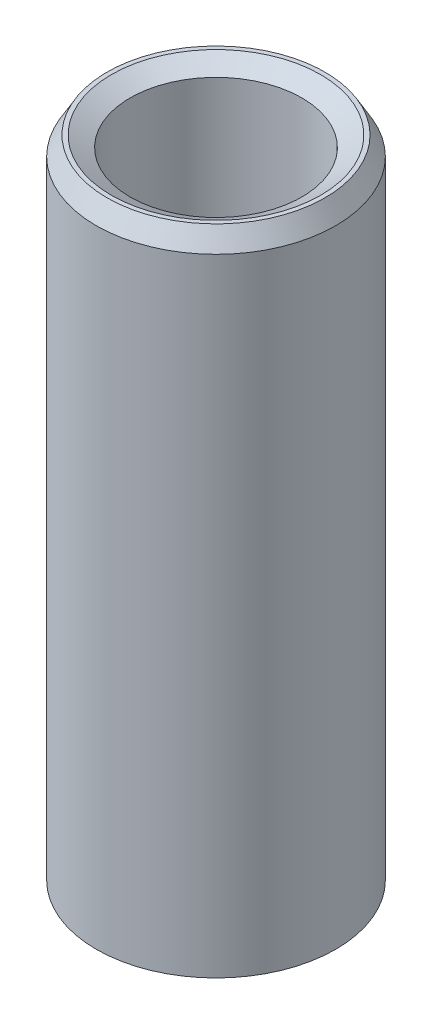
SolidWorks part; units mm, degrees
ref_plane "Front Plane" through (0, 0, 0) normal (0, 0, 1) x (1, 0, 0)
ref_plane "Top Plane" through (0, 0, 0) normal (0, 1, 0) x (1, 0, 0)
ref_plane "Right Plane" through (0, 0, 0) normal (1, 0, 0) x (0, 0, -1)
sketch "Sketch1" plane through (0, 0, 0) normal (0, 1, 0) x (1, 0, 0)
  circle A0 centre (0, 0) radius 25
  dimension "SLEEVE_OD" = 50
extrude "Boss-Extrude1" add sketch "Sketch1" along normal blind 136.993
sketch "Sketch2" plane through (0, 0, 0) normal (0, 1, 0) x (1, 0, 0)
  circle A0 centre (0, 0) radius 17.928
  dimension "BORE_D" = 35.8561
extrude "Cut-Extrude1" cut sketch "Sketch2" along normal through all
chamfer "Chamfer1" distance 3.9093 angle 30 4 edges at (0, 136.993, 17.928) (0, 0, 17.928) (0, 0, 25) (0, 136.993, 25) first distance on face at (0, 136.993, 17.928) first distance on face at (0, 0, 17.928) first distance on face at (0, 136.993, 25)
